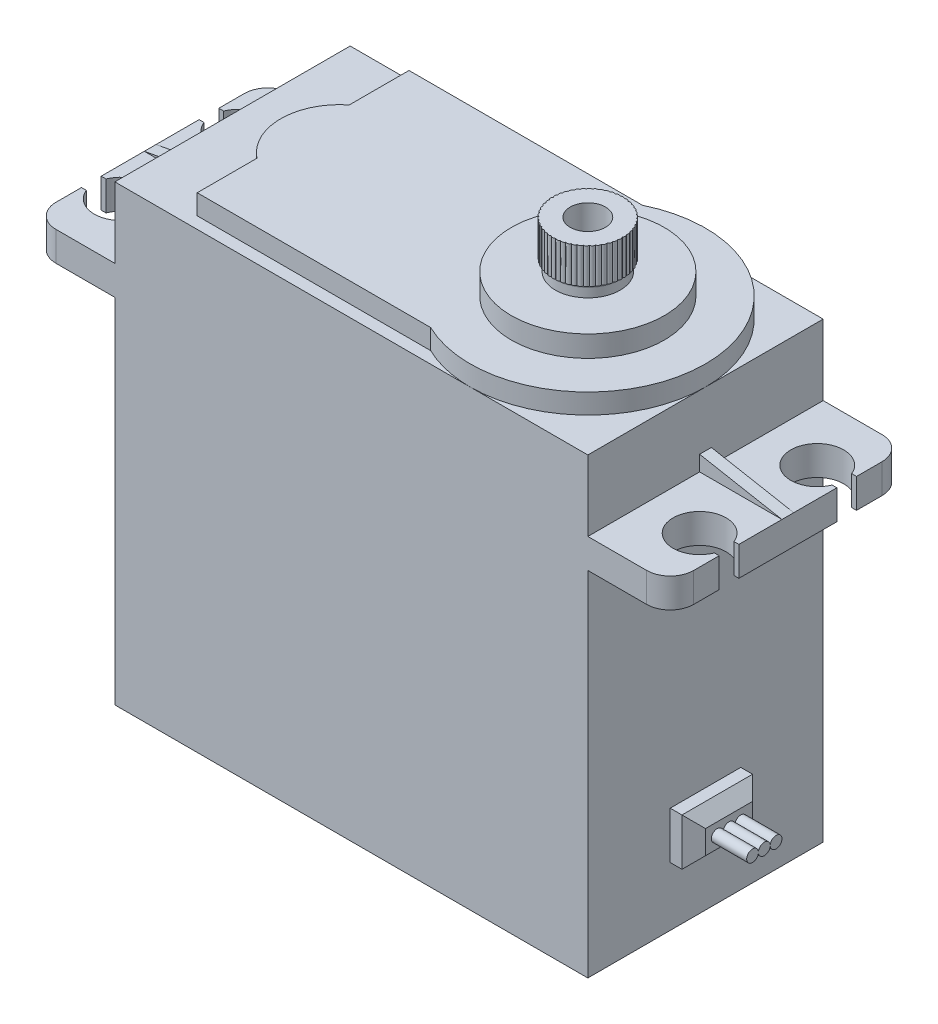
SolidWorks part; units mm, degrees
ref_plane "前视基准面" through (0, 0, 0) normal (0, 0, 1) x (1, 0, 0)
ref_plane "上视基准面" through (0, 0, 0) normal (0, 1, 0) x (1, 0, 0)
ref_plane "右视基准面" through (0, 0, 0) normal (1, 0, 0) x (0, 0, -1)
sketch "草图1" plane through (0, 0, 0) normal (0, 1, 0) x (1, 0, 0)
  line L1 (-20.1, 10) -> (20.1, 10)
  line L2 (-20.1, 10) -> (-20.1, -10)
  line L3 (-20.1, -10) -> (20.1, -10)
  line L4 (20.1, 10) -> (20.1, -10)
  line L5 (-20.1, 10) -> (20.1, -10) construction
  line L6 (-20.1, -10) -> (20.1, 10) construction
  point P0 (0, 0)
  dimension "D1" = 40.2
  dimension "D2" = 20
extrude "凸台-拉伸1" add sketch "草图1" along normal blind 8.5 and the other way blind 30
sketch "草图2" plane through (0, 0, 0) normal (0, 1, 0) x (1, 0, 0)
  line L1 (20.1, 10) -> (27.1, 10)
  line L2 (20.1, 10) -> (20.1, -10)
  line L3 (20.1, -10) -> (27.1, -10)
  line L4 (27.1, 10) -> (27.1, -10)
  dimension "D1" = 7
extrude "凸台-拉伸2" add sketch "草图2" along normal blind 2.5
sketch "草图3" plane through (0, 2.5, 0) normal (0, 1, 0) x (1, 0, 0)
  line L0 (-21.175, 0) -> (21.175, 0) construction
  line L1 (26.6886, 4.1631) -> (27.1, 4.1631)
  line L3 (26.6886, 5.8369) -> (27.1, 5.8369)
  line L4 (20.1, 10) -> (20.1, -10)
  line L5 (20.1, -10) -> (27.1, -10)
  line L6 (27.1, -10) -> (27.1, 10)
  line L7 (27.1, 10) -> (20.1, 10)
  line L10 (27.1, -5.8369) -> (27.1, -4.1631)
  line L13 (26.6886, -4.1631) -> (27.1, -4.1631)
  line L14 (26.6886, -5.8369) -> (27.1, -5.8369)
  line L15 (27.1, 4.1631) -> (27.1, 5.8369)
  line L16 (20.1, 10) -> (20.1, -10) construction
  arc A0 (26.6886, 5.8369) -> (26.6886, 4.1631) centre (24.6, 5) ccw
  arc A1 (26.6886, -5.8369) -> (26.6886, -4.1631) centre (24.6, -5) cw
  point P6 (25.6289, 5)
  dimension "D4" = 4.5
  dimension "D2" = 4.5
  dimension "D3" = 5
  dimension "D1" = 0
extrude "切除-拉伸1" cut sketch "草图3" against normal blind 2.5
mirror "镜向1" about plane through (0, 0, 0) normal (1, 0, 0) of "切除-拉伸1", "凸台-拉伸2"
fillet "圆角1" radius 2 4 edges at (-27.1, 1.25, 10) (-27.1, 1.25, -10) (27.1, 1.25, -10) (27.1, 1.25, 10)
sketch "草图4" plane through (0, 8.5, 0) normal (0, 1, 0) x (1, 0, 0)
  line L0 (20.1, 10) -> (-20.1, 10) construction
  line L1 (-20.1, -10) -> (20.1, -10) construction
  line L2 (20.1, -10) -> (20.1, 10) construction
  line L3 (-20.1, 10) -> (-20.1, -10) construction
  line L4 (-14.1, -9) -> (5.7411, -9)
  line L5 (-14.1, -9) -> (-14.1, -3.923)
  line L6 (-14.1, 9) -> (5.7411, 9)
  line L8 (-14.1, -9) -> (14.1, 9) construction
  line L9 (-14.1, 9) -> (14.1, -9) construction
  line L10 (-14.1, 3.923) -> (-14.1, 9)
  arc A0 (0.1002, 0.064) -> (0.1002, -0.064) centre (10.1, 0) ccw
  arc A1 (-14.1, 3.923) -> (-14.1, -3.923) centre (-11, 0) ccw
  arc A2 (5.7411, -9) -> (5.7411, 9) centre (10.1, 0) ccw
  point P8 (0, 0)
  dimension "D3" = 10
  dimension "D1" = 6
  dimension "D2" = 1
  dimension "D4" = 11
extrude "凸台-拉伸3" add sketch "草图4" along normal blind 1.7 contours A2 L6 L10 A1 L5 L4 region at (2.0972, 8.5, 0)
sketch "草图5" plane through (0, 10.2, 0) normal (0, 1, 0) x (1, 0, 0)
  arc A0 (5.7411, -9) -> (5.7411, 9) centre (10.1, 0) ccw construction
  arc A1 (5.7411, -9) -> (5.7411, 9) centre (10.1, 0) ccw
  circle A2 centre (10.1, 0) radius 6.5
  dimension "D1" = 13
extrude "凸台-拉伸4" add sketch "草图5" along normal blind 1.8 contours A2 region at (10.1, 10.2, 0)
sketch "草图6" plane through (0, 12, 0) normal (0, 1, 0) x (1, 0, 0)
  circle A0 centre (10.1, 0) radius 3
  dimension "D1" = 6
extrude "凸台-拉伸5" add sketch "草图6" along normal blind 4
sketch "草图7" plane through (0, 16, 0) normal (0, 1, 0) x (1, 0, 0)
  circle A0 centre (10.1, 0) radius 2.75 construction
  circle A1 centre (10.1, 0) radius 3
  circle A2 centre (10.1, 0) radius 3
  arc A3 (10.2837, 2.9196) -> (9.9163, 2.9196) centre (10.1, 2.75) ccw
  arc A4 (10.6482, 2.8735) -> (10.2837, 2.9196) centre (10.4447, 2.7283) ccw
  arc A5 (11.004, 2.7822) -> (10.6482, 2.8735) centre (10.7839, 2.6636) ccw
  arc A6 (11.3456, 2.6469) -> (11.004, 2.7822) centre (11.1123, 2.5569) ccw
  arc A7 (11.6675, 2.47) -> (11.3456, 2.6469) centre (11.4248, 2.4098) ccw
  arc A8 (11.9647, 2.254) -> (11.6675, 2.47) centre (11.7164, 2.2248) ccw
  arc A9 (12.2325, 2.0025) -> (11.9647, 2.254) centre (11.9825, 2.0047) ccw
  arc A10 (12.4667, 1.7195) -> (12.2325, 2.0025) centre (12.2189, 1.7529) ccw
  arc A11 (12.6635, 1.4093) -> (12.4667, 1.7195) centre (12.4219, 1.4735) ccw
  arc A12 (12.8199, 1.0769) -> (12.6635, 1.4093) centre (12.5883, 1.1709) ccw
  arc A13 (12.9335, 0.7275) -> (12.8199, 1.0769) centre (12.7154, 0.8498) ccw
  arc A14 (13.0023, 0.3666) -> (12.9335, 0.7275) centre (12.8013, 0.5153) ccw
  arc A15 (13.0254, 0) -> (13.0023, 0.3666) centre (12.8446, 0.1727) ccw
  arc A16 (13.0023, -0.3666) -> (13.0254, 0) centre (12.8446, -0.1727) ccw
  arc A17 (12.9335, -0.7275) -> (13.0023, -0.3666) centre (12.8013, -0.5153) ccw
  arc A18 (12.8199, -1.0769) -> (12.9335, -0.7275) centre (12.7154, -0.8498) ccw
  arc A19 (12.6635, -1.4093) -> (12.8199, -1.0769) centre (12.5883, -1.1709) ccw
  arc A20 (12.4667, -1.7195) -> (12.6635, -1.4093) centre (12.4219, -1.4735) ccw
  arc A21 (12.2325, -2.0025) -> (12.4667, -1.7195) centre (12.2189, -1.7529) ccw
  arc A22 (11.9647, -2.254) -> (12.2325, -2.0025) centre (11.9825, -2.0047) ccw
  arc A23 (11.6675, -2.47) -> (11.9647, -2.254) centre (11.7164, -2.2248) ccw
  arc A24 (11.3456, -2.6469) -> (11.6675, -2.47) centre (11.4248, -2.4098) ccw
  arc A25 (11.004, -2.7822) -> (11.3456, -2.6469) centre (11.1123, -2.5569) ccw
  arc A26 (10.6482, -2.8735) -> (11.004, -2.7822) centre (10.7839, -2.6636) ccw
  arc A27 (10.2837, -2.9196) -> (10.6482, -2.8735) centre (10.4447, -2.7283) ccw
  arc A28 (9.9163, -2.9196) -> (10.2837, -2.9196) centre (10.1, -2.75) ccw
  arc A29 (9.5518, -2.8735) -> (9.9163, -2.9196) centre (9.7553, -2.7283) ccw
  arc A30 (9.196, -2.7822) -> (9.5518, -2.8735) centre (9.4161, -2.6636) ccw
  arc A31 (8.8544, -2.6469) -> (9.196, -2.7822) centre (9.0877, -2.5569) ccw
  arc A32 (8.5325, -2.47) -> (8.8544, -2.6469) centre (8.7752, -2.4098) ccw
  arc A33 (8.2353, -2.254) -> (8.5325, -2.47) centre (8.4836, -2.2248) ccw
  arc A34 (7.9675, -2.0025) -> (8.2353, -2.254) centre (8.2175, -2.0047) ccw
  arc A35 (7.7333, -1.7195) -> (7.9675, -2.0025) centre (7.9811, -1.7529) ccw
  arc A36 (7.5365, -1.4093) -> (7.7333, -1.7195) centre (7.7781, -1.4735) ccw
  arc A37 (7.3801, -1.0769) -> (7.5365, -1.4093) centre (7.6117, -1.1709) ccw
  arc A38 (7.2665, -0.7275) -> (7.3801, -1.0769) centre (7.4846, -0.8498) ccw
  arc A39 (7.1977, -0.3666) -> (7.2665, -0.7275) centre (7.3987, -0.5153) ccw
  arc A40 (7.1746, 0) -> (7.1977, -0.3666) centre (7.3554, -0.1727) ccw
  arc A41 (7.1977, 0.3666) -> (7.1746, 0) centre (7.3554, 0.1727) ccw
  arc A42 (7.2665, 0.7275) -> (7.1977, 0.3666) centre (7.3987, 0.5153) ccw
  arc A43 (7.3801, 1.0769) -> (7.2665, 0.7275) centre (7.4846, 0.8498) ccw
  arc A44 (7.5365, 1.4093) -> (7.3801, 1.0769) centre (7.6117, 1.1709) ccw
  arc A47 (8.2353, 2.254) -> (7.9675, 2.0025) centre (8.2175, 2.0047) ccw
  arc A48 (8.5325, 2.47) -> (8.2353, 2.254) centre (8.4836, 2.2248) ccw
  arc A49 (8.8544, 2.6469) -> (8.5325, 2.47) centre (8.7752, 2.4098) ccw
  arc A50 (9.196, 2.7822) -> (8.8544, 2.6469) centre (9.0877, 2.5569) ccw
  arc A51 (9.5518, 2.8735) -> (9.196, 2.7822) centre (9.4161, 2.6636) ccw
  arc A52 (9.9163, 2.9196) -> (9.5518, 2.8735) centre (9.7553, 2.7283) ccw
  arc A53 (7.7333, 1.7195) -> (7.5365, 1.4093) centre (7.7781, 1.4735) ccw
  arc A55 (8.0259, 1.507) -> (7.9215, 1.6783) centre (7.7781, 1.4735) ccw [skipped]
  arc A65 (7.9675, 2.0025) -> (7.7333, 1.7195) centre (7.9811, 1.7529) ccw
  arc A73 (8.2311, 1.755) -> (8.149, 1.9381) centre (7.9811, 1.7529) ccw [skipped]
  circle M6 centre (10.1, 0) radius 3
  dimension "D2" = 5.5
  dimension "D1" = 0
  dimension "D3" = 50
extrude "切除-拉伸2" cut sketch "草图7" against normal blind 3 contours A50 A2 A49 | A51 A2 A50 | A52 A2 A51 | A52 A3 M6 | A4 A2 A3 | A5 A2 A4 | A6 A2 A5 | A48 A2 A47 | A49 A2 A48 | A65 A47 A2 | A65 A53 M6 | A53 A44 M6 | A43 A2 A42 | A42 A2 A41 | A44 A2 A43 | A41 A2 A40 | A40 A2 A39 | A39 A2 A38 | A38 A2 A37 | A37 A2 A36 | A36 A2 A35 | A35 A2 A34 | A34 A2 A33 | A33 A2 A32 | A32 A2 A31 | A31 A2 A30 | A30 A2 A29 | A29 A2 A28 | A28 A2 A27 | A27 A2 A26 | A26 A2 A25 | A25 A2 A24 | A24 A2 A23 | A23 A2 A22 | A22 A2 A21 | A21 A2 A20 | A20 A2 A19 | A19 A2 A18 | A18 A2 A17 | A17 A2 A16 | A16 A2 A15 | A15 A2 A14 | A14 A2 A13 | A13 A2 A12 | A12 A2 A11 | A11 A2 A10 | A10 A2 A9 | A9 A2 A8 | A8 A2 A7 | A7 A2 A6 region at (13.0777, 16, 0) region at (13.0543, 16, -0.3732) region at (13.0543, 16, 0.3732) region at (12.9842, 16, -0.7405) region at (12.9842, 16, 0.7405) region at (12.8686, 16, -1.0962) region at (12.8686, 16, 1.0962) region at (12.7094, 16, -1.4345) region at (12.7094, 16, 1.4345) region at (12.509, 16, -1.7503) region at (12.509, 16, 1.7503) region at (12.2707, 16, -2.0384) region at (12.2707, 16, 2.0384) region at (11.9981, 16, -2.2944) region at (11.9981, 16, 2.2944) region at (11.6956, 16, -2.5142) region at (11.6956, 16, 2.5142) region at (11.3679, 16, -2.6943) region at (11.3679, 16, 2.6943) region at (11.0202, 16, -2.832) region at (11.0202, 16, 2.832) region at (10.658, 16, -2.925) region at (10.658, 16, 2.925) region at (10.287, 16, -2.9719) region at (10.287, 16, 2.9719) region at (9.913, 16, -2.9719) region at (9.913, 16, 2.9719) region at (9.542, 16, -2.925) region at (9.542, 16, 2.925) region at (9.1798, 16, -2.832) region at (9.1798, 16, 2.832) region at (8.8321, 16, -2.6943) region at (8.8321, 16, 2.6943) region at (8.5044, 16, -2.5142) region at (8.5044, 16, 2.5142) region at (8.2019, 16, -2.2944) region at (8.2019, 16, 2.2944) region at (7.9293, 16, -2.0384) region at (7.9293, 16, 2.0384) region at (7.691, 16, -1.7503) region at (7.691, 16, 1.7503) region at (7.4906, 16, -1.4345) region at (7.4906, 16, 1.4345) region at (7.3314, 16, -1.0962) region at (7.3314, 16, 1.0962) region at (7.2158, 16, -0.7405) region at (7.2158, 16, 0.7405) region at (7.1457, 16, -0.3732) region at (7.1457, 16, 0.3732) region at (7.1223, 16, 0)
sketch "草图8" plane through (0, 12, 0) normal (0, 1, 0) x (1, 0, 0)
  circle A0 centre (10.1, 0) radius 3 construction
  circle A1 centre (10.1, 0) radius 3
  circle A2 centre (10.1, 0) radius 2.75
  circle A3 centre (10.1, 0) radius 3
  circle M3 centre (10.1, 0) radius 3
  dimension "D1" = 5.5
extrude "切除-拉伸4" cut sketch "草图8" along normal blind 1 contours A2 M3 region at (7.1849, 12, 0)
fillet "圆角2" radius 0.23 1 edges at (10.1, 13, 2.75)
sketch "草图9" plane through (20.1, 0, 0) normal (1, 0, 0) x (0, 0, -1)
  line L0 (-10, -30) -> (10, -30) construction
  line L1 (-3, -21) -> (3, -21)
  line L2 (-3, -21) -> (-3, -25)
  line L3 (-3, -25) -> (3, -25)
  line L4 (3, -21) -> (3, -25)
  line L5 (-3, -21) -> (3, -25) construction
  line L6 (-3, -25) -> (3, -21) construction
  point P0 (0, -23)
  dimension "D1" = 6
  dimension "D2" = 4
  dimension "D3" = 5
extrude "凸台-拉伸6" add sketch "草图9" along normal blind 2
chamfer "倒角1" distance 1 angle 45 4 edges at (22.1, -23, -3) (22.1, -25, 0) (22.1, -23, 3) (22.1, -21, 0)
sketch "草图10" plane through (22.1, 0, 0) normal (1, 0, 0) x (0, 0, -1)
  line L0 (2, -22) -> (-2, -22) construction
  line L1 (-2, -22) -> (-2, -24) construction
  line L2 (0.492, -22.9111) -> (0.508, -22.9111)
  line L3 (-0.508, -23.0889) -> (-0.492, -23.0889)
  line L5 (-0.508, -22.9111) -> (-0.492, -22.9111)
  line L7 (-0.502, -23.0446) -> (-0.498, -23.0443) construction
  line L8 (-0.502, -22.9554) -> (-0.498, -22.9557) construction
  line L9 (0.498, -23.0443) -> (0.502, -23.0446) construction
  line L10 (0.498, -22.9557) -> (0.502, -22.9554) construction
  line L11 (0.492, -23.0889) -> (0.508, -23.0889)
  arc A0 (-0.492, -23.0889) -> (0.492, -23.0889) centre (0, -23) ccw
  arc A1 (0.508, -23.0889) -> (0.508, -22.9111) centre (1, -23) ccw
  arc A2 (-0.508, -22.9111) -> (-0.508, -23.0889) centre (-1, -23) ccw
  arc A3 (0.492, -22.9111) -> (-0.492, -22.9111) centre (0, -23) ccw
  point P9 (0, -22)
  point P12 (-2, -23)
  dimension "D1" = 1
extrude "凸台-拉伸8" add sketch "草图10" along normal blind 3
sketch "草图11" plane through (0, 16, 0) normal (0, 1, 0) x (1, 0, 0)
  circle A1 centre (10.1, 0) radius 1.5
  dimension "D1" = 3
extrude "切除-拉伸5" cut sketch "草图11" against normal blind 3
sketch "草图13" plane through (0, 0, 0) normal (0, 0, 1) x (1, 0, 0)
  line L0 (20.1, 3.8) -> (20.1, 2.5)
  line L1 (20.1, 2.5) -> (20.1, 8.5) construction
  line L2 (20.1, 2.5) -> (27.1, 2.5)
  line L3 (27.1, 2.5) -> (20.1, 3.8)
  dimension "D1" = 1.3
extrude "凸台-拉伸9" add sketch "草图13" along normal blind 0.5 and the other way blind 0.5
mirror "镜向2" about plane through (0, 0, 0) normal (1, 0, 0) of "凸台-拉伸9"
